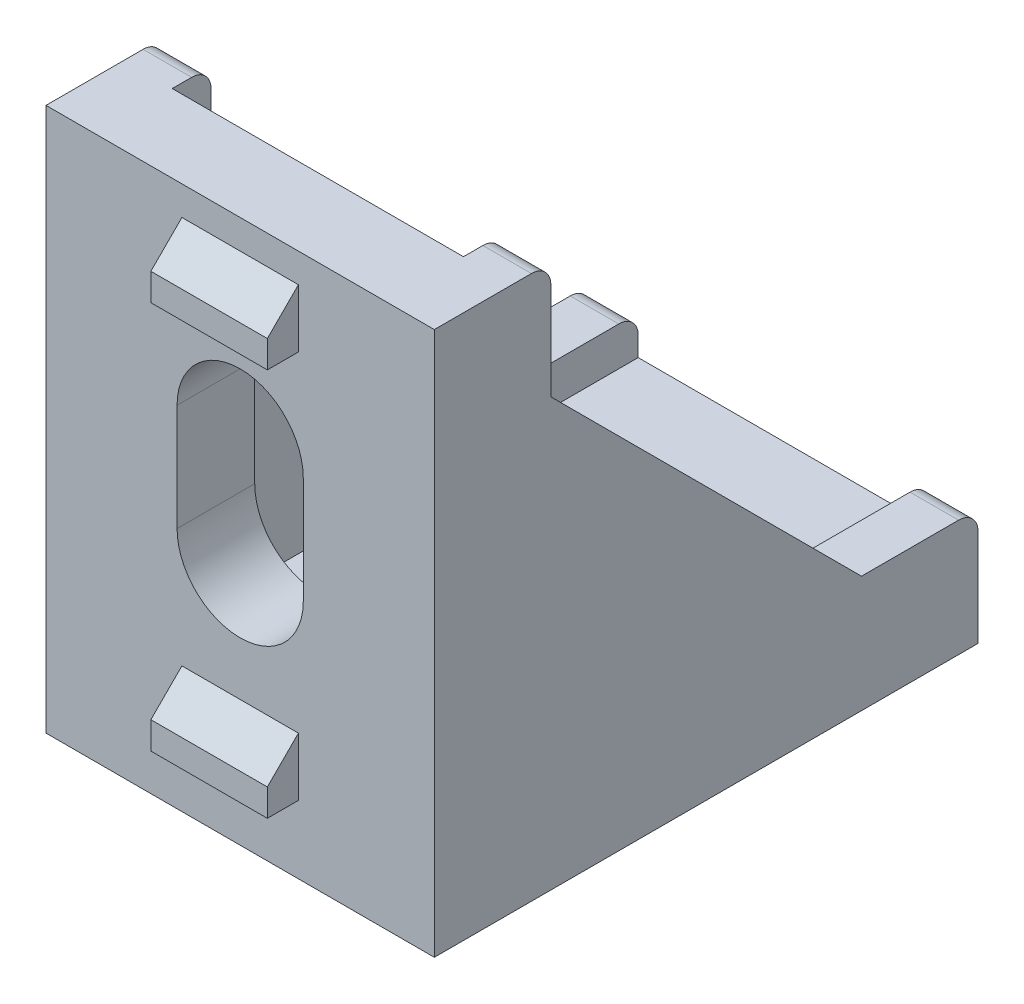
SolidWorks part; units mm, degrees
ref_plane "Front Plane" through (0, 0, 0) normal (0, 0, 1) x (1, 0, 0)
ref_plane "Top Plane" through (0, 0, 0) normal (0, 1, 0) x (1, 0, 0)
ref_plane "Right Plane" through (0, 0, 0) normal (1, 0, 0) x (0, 0, -1)
sketch "Sketch1" plane through (0, 0, 0) normal (0, 0, 1) x (1, 0, 0)
  line L0 (-10, 6) -> (7.5, 6)
  line L1 (7.5, 6) -> (7.5, 22)
  line L2 (7.5, 22) -> (-10, 22)
  line L3 (-10, 22) -> (-10, 6)
extrude "Boss-Extrude1" add sketch "Sketch1" against normal blind 6
sketch "Sketch2" plane through (0, 0, -6) normal (0, 0, -1) x (-1, 0, 0)
  line L0 (10, 22) -> (10, 6)
  line L1 (10, 6) -> (7.5, 6)
  line L2 (7.5, 6) -> (7.5, 22)
  line L3 (7.5, 22) -> (10, 22)
extrude "Boss-Extrude2" add sketch "Sketch2" along normal blind 22
sketch "Sketch3" plane through (7.5, 0, 0) normal (1, 0, 0) x (0, 0, -1)
  line L0 (6, 22) -> (22, 6)
  line L1 (22, 6) -> (0, 6)
  line L2 (0, 6) -> (0, 22)
  line L3 (0, 22) -> (6, 22)
extrude "Boss-Extrude3" add sketch "Sketch3" along normal blind 2.5
sketch "Sketch4" plane through (0, 22, 0) normal (0, 1, 0) x (-1, 0, 0)
  line L0 (7.5, -6) -> (-10, -6)
  line L1 (-10, -6) -> (-10, 0)
  line L2 (-10, 0) -> (10, 0)
  line L3 (10, 0) -> (10, -28)
  line L4 (10, -28) -> (7.5, -28)
  line L5 (7.5, -28) -> (7.5, -6)
extrude "Boss-Extrude4" add sketch "Sketch4" along normal blind 6
sketch "Sketch5" plane through (0, 6, 0) normal (0, -1, 0) x (1, 0, 0)
  line L0 (-10, 0) -> (10, 0)
  line L1 (10, 0) -> (10, -28)
  line L2 (10, -28) -> (-10, -28)
  line L3 (-10, -28) -> (-10, 0)
extrude "Boss-Extrude5" add sketch "Sketch5" along normal blind 6
ref_plane "Plane1" through (0, 0, -6) normal (0, 0, -1) x (-1, 0, 0)
ref_plane "Plane2" through (0, 0, -4) normal (0, 0, 1) x (1, 0, 0)
sketch "Sketch7" plane through (0, 0, -4) normal (0, 0, 1) x (1, 0, 0)
  line L0 (-7.5, 6) -> (7.5, 6)
  line L1 (7.5, 6) -> (7.5, 28)
  line L2 (7.5, 28) -> (-7.5, 28)
  line L3 (-7.5, 28) -> (-7.5, 6)
extrude "Cut-Extrude1" cut sketch "Sketch7" against normal up to surface up to plane "Plane1"
ref_plane "Plane3" through (0, 6, 0) normal (0, 1, 0) x (1, 0, 0)
ref_plane "Plane4" through (0, 4, 0) normal (0, -1, 0) x (1, 0, 0)
sketch "Sketch9" plane through (0, 4, 0) normal (0, -1, 0) x (1, 0, 0)
  line L0 (-7.5, -4) -> (-7.5, -28)
  line L1 (-7.5, -28) -> (7.5, -28)
  line L2 (7.5, -28) -> (7.5, -4)
  line L3 (7.5, -4) -> (-7.5, -4)
extrude "Cut-Extrude2" cut sketch "Sketch9" against normal up to surface up to plane "Plane3"
sketch "Sketch10" plane through (-10, 0, 0) normal (-1, 0, 0) x (0, 0, 1)
  line L0 (-28, 28) -> (-28, 6)
  line L1 (-28, 6) -> (-22, 6)
  line L2 (-22, 6) -> (-6, 22)
  line L3 (-6, 22) -> (-6, 28)
  line L4 (-6, 28) -> (-28, 28)
extrude "Cut-Extrude3" cut sketch "Sketch10" against normal through all
sketch "Sketch11" plane through (0, 0, -4) normal (0, 0, -1) x (-1, 0, 0)
  line L0 (3.25, 12.5) -> (3.25, 18)
  line L1 (-3.25, 18) -> (-3.25, 12.5)
  line L2 (10, 0) -> (-10, 0) construction
  arc A0 (3.25, 18) -> (-3.25, 18) centre (0, 18) ccw
  arc A1 (-3.25, 12.5) -> (3.25, 12.5) centre (0, 12.5) ccw
  point P8 (0, 0)
  point P9 (0, 0)
  dimension "D1" = 12.5
  dimension "D2" = 5.5
extrude "Cut-Extrude4" cut sketch "Sketch11" against normal through all
sketch "Sketch12" plane through (0, 0, 0) normal (0, -1, 0) x (1, 0, 0)
  line L0 (3.25, -18) -> (3.25, -12.5)
  line L1 (-3.25, -12.5) -> (-3.25, -18)
  arc A0 (-3.25, -18) -> (3.25, -18) centre (0, -18) ccw
  arc A1 (3.25, -12.5) -> (-3.25, -12.5) centre (0, -12.5) ccw
extrude "Cut-Extrude5" cut sketch "Sketch12" against normal through all
ref_plane "Plane5" through (3, 0, 0) normal (1, 0, 0) x (0, 0, -1)
sketch "Sketch13" plane through (3, 0, 0) normal (1, 0, 0) x (0, 0, -1)
  line L0 (0, 26.5) -> (-1.6, 24.9)
  line L1 (-1.6, 24.9) -> (-1.6, 23.5)
  line L2 (-1.6, 23.5) -> (0, 23.5)
  line L3 (0, 23.5) -> (0, 26.5)
extrude "Boss-Extrude6" add sketch "Sketch13" against normal blind 6
sketch "Sketch14" plane through (3, 0, 0) normal (1, 0, 0) x (0, 0, -1)
  line L0 (0, 6.5) -> (-1.6, 4.9)
  line L1 (-1.6, 4.9) -> (-1.6, 3.5)
  line L2 (-1.6, 3.5) -> (0, 3.5)
  line L3 (0, 3.5) -> (0, 6.5)
extrude "Boss-Extrude7" add sketch "Sketch14" against normal blind 6
sketch "Sketch15" plane through (3, 0, 0) normal (1, 0, 0) x (0, 0, -1)
  line L0 (23.5, 0) -> (23.5, -1.6)
  line L1 (23.5, -1.6) -> (24.9, -1.6)
  line L2 (24.9, -1.6) -> (26.5, 0)
  line L3 (26.5, 0) -> (23.5, 0)
extrude "Boss-Extrude8" add sketch "Sketch15" against normal blind 6
sketch "Sketch16" plane through (3, 0, 0) normal (1, 0, 0) x (0, 0, -1)
  line L0 (3.5, 0) -> (3.5, -1.6)
  line L1 (3.5, -1.6) -> (4.9, -1.6)
  line L2 (4.9, -1.6) -> (6.5, 0)
  line L3 (6.5, 0) -> (3.5, 0)
extrude "Boss-Extrude9" add sketch "Sketch16" against normal blind 6
fillet "Fillet1" radius 1 4 edges at (-8.75, 6, -28) (8.75, 6, -28) (-8.75, 28, -6) (8.75, 28, -6) tangent propagation no
